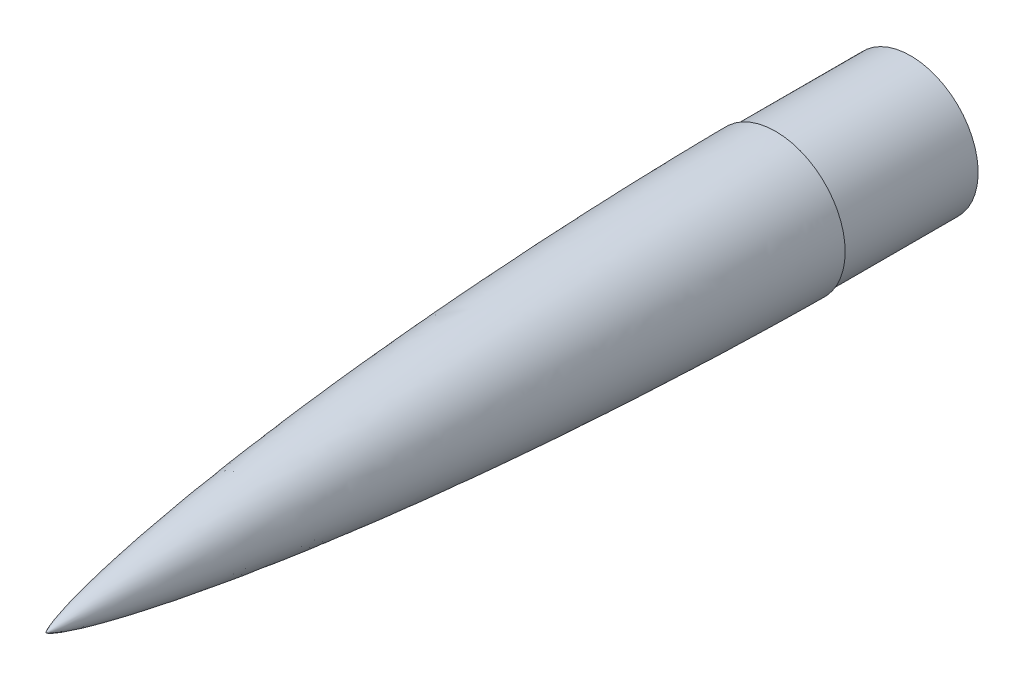
SolidWorks part; units mm, degrees
ref_plane "Front Plane" through (0, 0, 0) normal (0, 0, 1) x (1, 0, 0)
ref_plane "Top Plane" through (0, 0, 0) normal (0, 1, 0) x (1, 0, 0)
ref_plane "Right Plane" through (0, 0, 0) normal (1, 0, 0) x (0, 0, -1)
sketch "Sketch2" plane through (0, 0, 0) normal (1, 0, 0) x (0, 0, -1)
  line L2 (0, 0) -> (685.8, 0)
  line L3 (685.8, 0) -> (685.8, 65.405)
  spline S0 degree 4 poles (0, 0) (0.0025, 0.0089) (0.0093, 0.0259) (0.0295, 0.0571) (0.0636, 0.1004) (0.1077, 0.1476) (0.1715, 0.2089) (0.2498, 0.2765) (0.3425, 0.3499) (0.4498, 0.4286) (0.6199, 0.5462) (0.8271, 0.6777) (1.0716, 0.822) (1.4784, 1.047) (2.1234, 1.377) (3.293, 1.9175) (5.4483, 2.7978) (9.3183, 4.1819) (16.2109, 6.3166) (27.735, 9.3896) (47.6298, 13.9525) (76.2047, 19.5039) (112.0403, 25.4688) (153.2894, 31.4017) (195.7228, 36.7544) (238.2285, 41.4957) (280.7895, 45.7076) (323.3947, 49.4447) (366.0357, 52.7471) (408.7061, 55.6442) (446.0638, 57.844) (478.0972, 59.5006) (510.1392, 60.9782) (536.8474, 62.0623) (563.561, 63.001) (592.9512, 63.8726) (614.3287, 64.4025) (632.9927, 64.784) (648.9421, 65.0475) (658.1886, 65.1767) (666.0773, 65.2692) (672.6514, 65.3317) (677.9108, 65.3735) (681.8554, 65.3935) (684.4851, 65.405) (685.8, 65.405) knots 0 0 0 0 0 0.000053 0.000107 0.000213 0.00032 0.000426 0.000619 0.000812 0.001004 0.001197 0.001816 0.002232 0.002648 0.003889 0.00601 0.00969 0.016124 0.027679 0.047778 0.078732 0.134288 0.196196 0.258104 0.320012 0.38192 0.443828 0.505737 0.567645 0.629553 0.691461 0.722415 0.753369 0.815277 0.846231 0.877185 0.923616 0.939093 0.95432 0.969547 0.97716 0.984773 0.992387 1 1 1 1 1 construction
  spline S1 degree 4 poles (0, 0) (0.0025, 0.0089) (0.0093, 0.0259) (0.0295, 0.0571) (0.0636, 0.1004) (0.1077, 0.1476) (0.1715, 0.2089) (0.2498, 0.2765) (0.3425, 0.3499) (0.4498, 0.4286) (0.6199, 0.5462) (0.8271, 0.6777) (1.0716, 0.822) (1.4784, 1.047) (2.1234, 1.377) (3.293, 1.9175) (5.4483, 2.7978) (9.3183, 4.1819) (16.2109, 6.3166) (27.735, 9.3896) (47.6298, 13.9525) (76.2047, 19.5039) (112.0403, 25.4688) (153.2894, 31.4017) (195.7228, 36.7544) (238.2285, 41.4957) (280.7895, 45.7076) (323.3947, 49.4447) (366.0357, 52.7471) (408.7061, 55.6442) (446.0638, 57.844) (478.0972, 59.5006) (510.1392, 60.9782) (536.8474, 62.0623) (563.561, 63.001) (592.9512, 63.8726) (614.3287, 64.4025) (632.9927, 64.784) (648.9421, 65.0475) (658.1886, 65.1767) (666.0773, 65.2692) (672.6514, 65.3317) (677.9108, 65.3735) (681.8554, 65.3935) (684.4851, 65.405) (685.8, 65.405) knots 0 0 0 0 0 0.000053 0.000107 0.000213 0.00032 0.000426 0.000619 0.000812 0.001004 0.001197 0.001816 0.002232 0.002648 0.003889 0.00601 0.00969 0.016124 0.027679 0.047778 0.078732 0.134288 0.196196 0.258104 0.320012 0.38192 0.443828 0.505737 0.567645 0.629553 0.691461 0.722415 0.753369 0.815277 0.846231 0.877185 0.923616 0.939093 0.95432 0.969547 0.97716 0.984773 0.992387 1 1 1 1 1
  dimension "D1" = 65.405
  dimension "D2" = 685.8
revolve "Revolve1" add sketch "Sketch2" angle 360 about L2
shell "Shell1" thickness 2.032 removed face at (65.405, 0, -685.8)
sketch "Sketch3" plane through (0, 0, -685.8) normal (0, 0, -1) x (-1, 0, 0)
  circle A0 centre (0, 0) radius 63.373 construction
  circle A1 centre (0, 0) radius 63.373
  circle A2 centre (0, 0) radius 61.595
  dimension "D1" = 123.19
extrude "Boss-Extrude1" add sketch "Sketch3" along normal blind 127 and the other way up to next
equation "\"AIRFRAME_OD\"= 5.15in"
equation "\"AIRFRAME_ID\"= 4.99in"
equation "\"FLAT_T\"= 0.125in"
equation "\"NOSE_EXP_L\"= 27in"
equation "\"NOSE_SHOULDER_L\"= 5in"
equation "\"MAIN_L\"= 30in"
equation "\"RECO_COUP_L\"= 10in"
equation "\"RECO_SWITCH_L\"= 2in"
equation "\"DROGUE_L\"= 20in"
equation "\"ATS_FORE_COUP_L\"= 5.5in"
equation "\"ATS_AFT_COUP_L\"= 4.5in"
equation "\"LOWER_L\"= 30in"
equation "\"FIN_N\"= 4"
equation "\"CR_AFT_X\"= 0.5in"
equation "\"CR_FORE_X\"= 9.25in"
equation "\"COUPLER_OD\"= 4.998in"
equation "\"COUPLER_ID\"= 4.85in"
equation "\"RECO_ROD_X\"= 3.5in"
equation "\"ATS_ROD_X\"= 3.75in"
equation "\"FIN_ROOT\"= 8in"
equation "\"FIN_X\"= 0.75in"
equation "\"MOTOR_OD\"= 3.091in"
equation "\"MOTOR_ID\"= 3.00in"
equation "\"MOTOR_L\"= 14in"
equation "\"MOTOR_LOWER_X\"= 2in"
equation "\"NOSE_CONE_L\"=14.5in"
equation "\"D1@Shell1\"=(\"AIRFRAME_OD\"-\"AIRFRAME_ID\")/2"
equation "\"D1@Boss-Extrude1\"= \"NOSE_SHOULDER_L\""
equation "\"D1@Sketch2\"=\"AIRFRAME_OD\"/2"
equation "\"D1@Sketch3\"=\"COUPLER_ID\""
